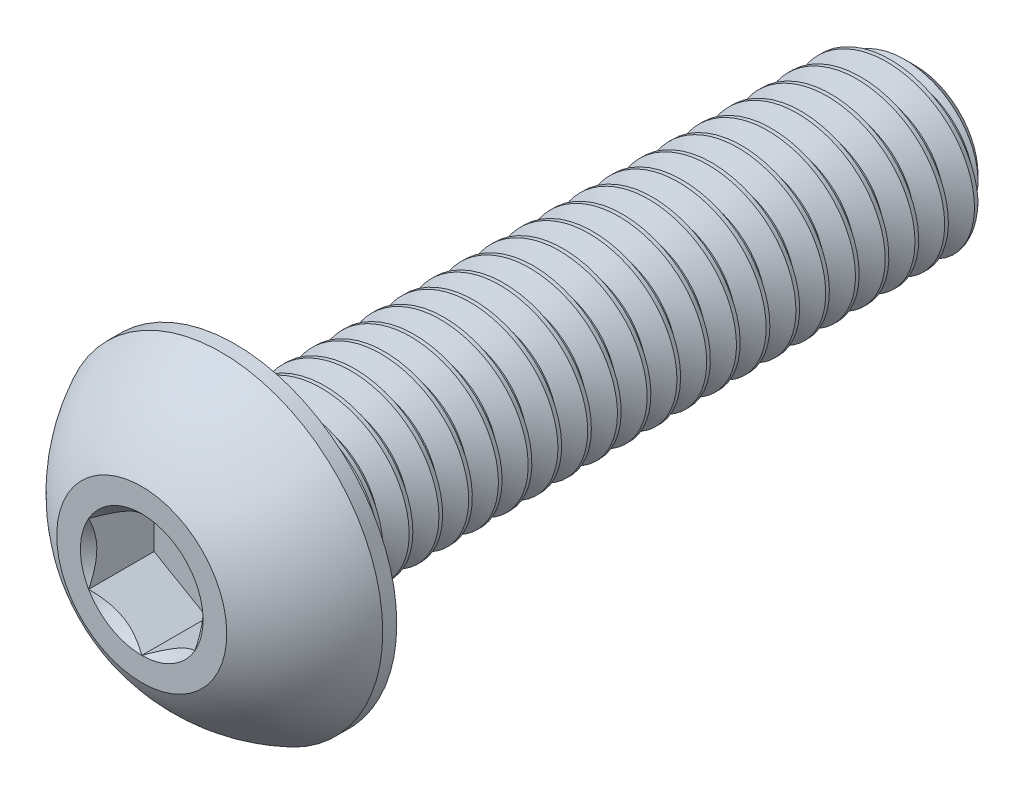
SolidWorks part; units mm, degrees
ref_plane "Front" through (0, 0, 0) normal (0, 0, 1) x (1, 0, 0)
ref_plane "Top" through (0, 0, 0) normal (0, 1, 0) x (1, 0, 0)
ref_plane "Right" through (0, 0, 0) normal (1, 0, 0) x (0, 0, -1)
sketch "Sketch1" plane through (0, 0, 0) normal (1, 0, 0) x (0, 0, -1)
  line L2 (2.2, 2) -> (18.2, 2)
  line L3 (18.2, 2) -> (18.2, 0)
  line L4 (18.2, 0) -> (2.2, 0)
  line L6 (1.87, 3.8) -> (2.2, 3.8) construction
  line L7 (18.2, 2) -> (18.2, -2) construction
  line L8 (0, 0) -> (2.2, 0) construction
  line L9 (2.2, 3.8) -> (2.2, -3.8) construction
  line L11 (2.2, 2) -> (2.2, 0)
  line L13 (0, 1.25) -> (0, -1.25) construction
  line L14 (0, 1.25) -> (0, 2) construction
  arc A3 (0, 2) -> (1.87, 3.8) centre (3.7264, 0) cw construction
  dimension "D1" = 0.33
  dimension "Head Ht" = 2.2
  dimension "Head Dia" = 7.6
  dimension "Dia" = 4
  dimension "Lg" = 16
  dimension "Hex" = 2.5
revolve "Revolve1" add sketch "Sketch1" angle 360 mid plane about L4
sketch "Sketch3" plane through (0, 0, -18.2) normal (0, 0, -1) x (-1, 0, 0)
  circle A0 centre (0, 0) radius 2
curve "Helix/Spiral1" pitch 0.7 height 16.7 radius 2 centre (0, 0, -18.2) axis (0, 0, 1) start towards (0, 1, 0)
sketch "Sketch2" plane through (0, 0, 0) normal (1, 0, 0) x (0, 0, -1)
  line L0 (18.2, 2) -> (18.8125, 2)
  line L1 (18.8125, 2) -> (18.55, 1.5453)
  line L2 (18.55, 1.5453) -> (18.4625, 1.5453)
  line L3 (18.4625, 1.5453) -> (18.2, 2)
  line L4 (18.3313, 1.7727) -> (18.6812, 1.7727) construction
  dimension "D1" = 60
  dimension "D2" = 0.0875
  dimension "D3" = 0.35
chamfer "Chamfer1" distance 0.525 angle 45 1 edges at (0, 2, -18.2)
sweep "Cut-Sweep1" cut profiles "Sketch2" path "Helix/Spiral1"
sketch "Sketch7" plane through (0, 0, 0) normal (1, 0, 0) x (0, 0, -1)
  line L6 (1.87, 3.8) -> (2.2, 3.8) construction
  line L8 (0, 0) -> (2.2, 0) construction
  line L11 (2.2, 3.8) -> (2.2, -3.8) construction
  line L12 (1.87, 3.8) -> (2.2, 3.8)
  line L13 (0, 0) -> (2.2, 0)
  line L14 (0, 1.25) -> (0, -1.25) construction
  line L15 (2.2, 3.8) -> (2.2, 0)
  line L16 (0, 2) -> (0, 0)
  arc A2 (1.87, 3.8) -> (0, 2) centre (3.7264, 0) ccw construction
  arc A3 (1.87, 3.8) -> (0, 2) centre (3.7264, 0) ccw
revolve "Revolve2" add sketch "Sketch7" angle 360 mid plane about L13
sketch "Sketch5" plane through (0, 0, 0) normal (0, 0, 1) x (1, 0, 0)
  line L1 (1.25, -0.7217) -> (1.25, 0.7217)
  line L2 (1.25, 0.7217) -> (0, 1.4434)
  line L3 (0, 1.4434) -> (-1.25, 0.7217)
  line L4 (-1.25, 0.7217) -> (-1.25, -0.7217)
  line L5 (-1.25, -0.7217) -> (0, -1.4434)
  line L6 (0, -1.4434) -> (1.25, -0.7217)
  circle A0 centre (0, 0) radius 1.25 construction
extrude "Cut-Extrude2" cut sketch "Sketch5" against normal blind 1.54
sketch "Sketch6" plane through (0, 0, 0) normal (0, 0, 1) x (1, 0, 0)
  circle A0 centre (0, 0) radius 1.4434
extrude "Cut-Extrude3" cut sketch "Sketch6" against normal blind 1.54 draft 45
sketch "Sketch9" [suppressed] plane through (0, 0, -6.6) normal (0, 0, 1) x (1, 0, 0)
  circle A2 centre (0, 0) radius 6
extrude "Boss-Extrude2" [suppressed] add sketch "Sketch9" against normal offset from surface (19 mm away) 32 up to face at (0, 1.475, -18.2)
sketch "Sketch10" plane through (0, 0, 0) normal (1, 0, 0) x (0, 0, -1)
  line L0 (18.2, 2) -> (18.2, -2) construction
  point P0 (17.15, -2)
  dimension "D1" = 1.05
equation "\"D3@Helix/Spiral1\" = \"Lg@Sketch1\" + \"D4@Helix/Spiral1\""
equation "\"D2@Sketch2\" = \"D4@Helix/Spiral1\" * .125"
equation "\"D3@Sketch2\" = \"D4@Helix/Spiral1\" * .5"
equation "\"D1@Chamfer1\" = \"D4@Helix/Spiral1\" * .75"
equation "\"D1@Cut-Extrude2\" = \"Head Ht@Sketch1\" * .7"
equation "\"D1@Sketch1\" = \"Head Ht@Sketch1\" * .15"
equation "\"D1@Sketch10\" = \"D4@Helix/Spiral1\" * 1.5"
equation "\"D1@Cut-Extrude3\" = \"D1@Cut-Extrude2\""
